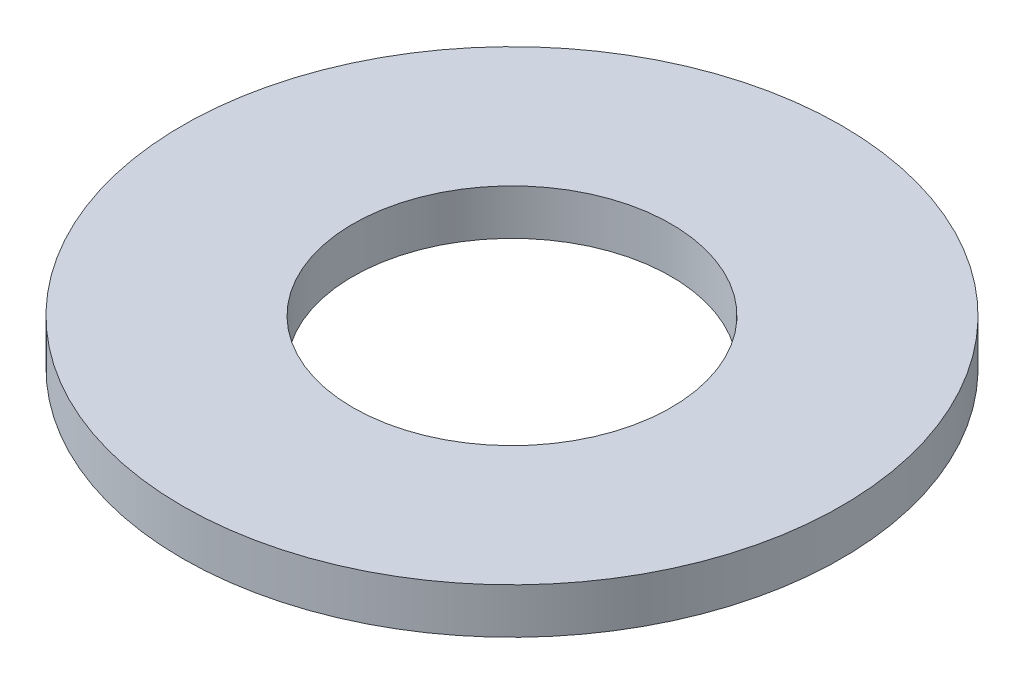
SolidWorks part; units mm, degrees
ref_plane "Front Plane" through (0, 0, 0) normal (0, 0, 1) x (1, 0, 0)
ref_plane "Top Plane" through (0, 0, 0) normal (0, 1, 0) x (1, 0, 0)
ref_plane "Right Plane" through (0, 0, 0) normal (1, 0, 0) x (0, 0, -1)
sketch "Sketch1" plane through (0, 0, 0) normal (0, 1, 0) x (1, 0, 0)
  circle A0 centre (0, 0) radius 72.5
  dimension "FLANGE_OD" = 145
extrude "Boss-Extrude1" add sketch "Sketch1" along normal blind 10
sketch "Sketch2" plane through (0, 0, 0) normal (0, 1, 0) x (1, 0, 0)
  circle A0 centre (0, 0) radius 35
  dimension "BORE_D" = 70
extrude "Cut-Extrude1" cut sketch "Sketch2" along normal through all
sketch "Sketch3" plane through (0, 10, 0) normal (0, 1, 0) x (1, 0, 0)
  circle A0 centre (0, 0) radius 28.3451 construction
  circle A1 centre (-28.3451, 0) radius 1.612
  dimension "BOLT_D" = 3.224
  dimension "BOLT_PCD" = 56.6902
extrude "Cut-Extrude2" cut sketch "Sketch3" against normal blind 9.5661 rebuild error yes
pattern_circular "CirPattern1" count 4 over 360 rebuild error yes
